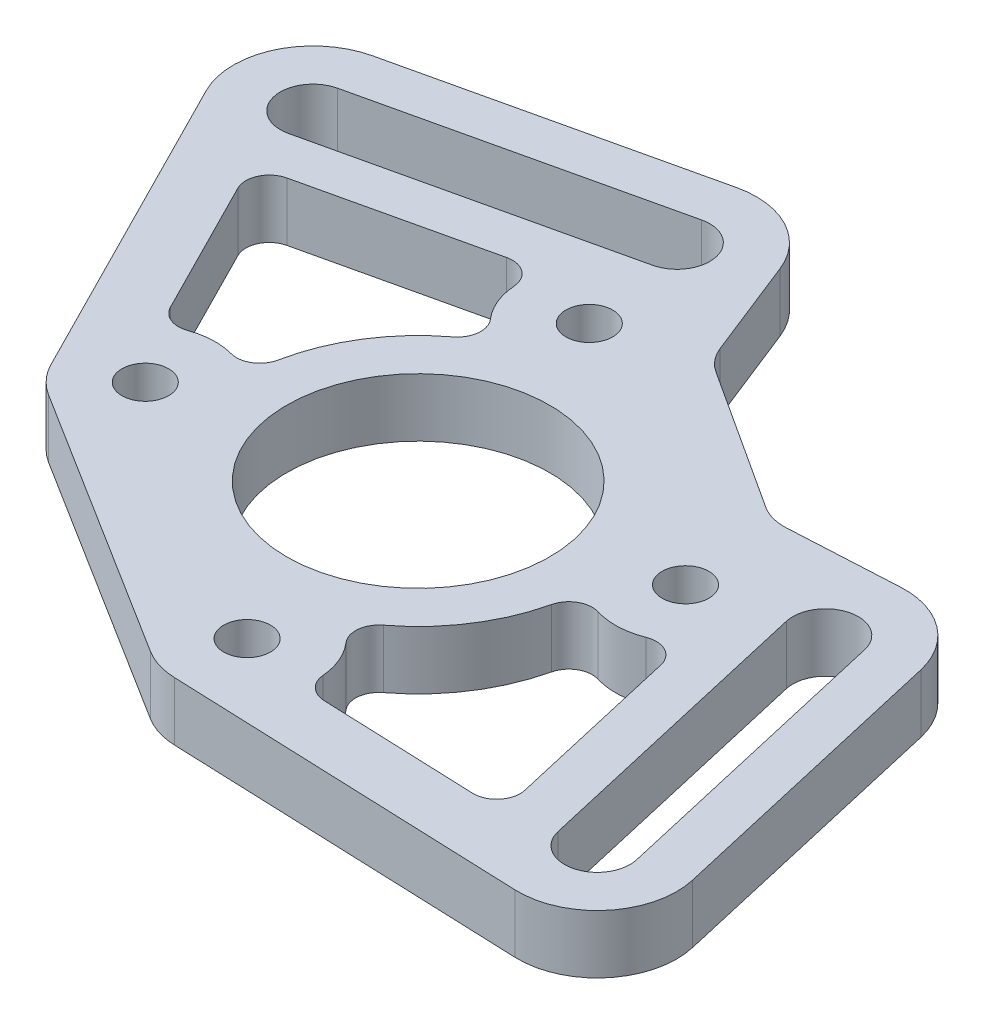
SolidWorks part; units mm, degrees
ref_plane "Front Plane" through (0, 0, 0) normal (0, 0, 1) x (1, 0, 0)
ref_plane "Top Plane" through (0, 0, 0) normal (0, 1, 0) x (1, 0, 0)
ref_plane "Right Plane" through (0, 0, 0) normal (1, 0, 0) x (0, 0, -1)
sketch "Sketch1" plane through (0, 0, 0) normal (0, 1, 0) x (1, 0, 0)
  line L0 (9.2897, 14.4451) -> (11.6941, 18.1838) construction
  line L2 (-10.3015, 44.9223) -> (-42.4861, 37.5417)
  line L3 (45.0868, 9.5277) -> (52.4673, -22.6569)
  line L4 (-5.5326, 24.1261) -> (24.2906, 4.7587) construction
  line L5 (-5.5326, 24.1261) -> (5.5326, -24.1261) construction
  line L6 (36.6692, 7.5974) -> (44.0498, -24.5872) construction
  line L7 (40.1353, 8.3922) -> (47.5158, -23.7924)
  line L8 (33.2032, 6.8025) -> (40.5838, -25.382)
  line L9 (24.2906, 4.7587) -> (36.6692, 7.5974) construction
  line L10 (-6.9454, 30.2884) -> (30.3335, 6.0792) construction
  line L11 (30.3335, 6.0792) -> (6.1243, -31.1997) construction
  line L12 (6.1243, -31.1997) -> (-31.1546, -6.9905) construction
  line L13 (-31.1546, -6.9905) -> (-6.9454, 30.2884) construction
  line L14 (-5.5326, 24.1261) -> (-8.3712, 36.5048) construction
  line L15 (-8.3712, 36.5048) -> (-40.5558, 29.1242) construction
  line L16 (9.2897, 14.4451) -> (0, 0) construction
  line L17 (-7.5764, 33.0387) -> (-39.761, 25.6582)
  line L18 (-9.1661, 39.9708) -> (-41.3507, 32.5902)
  line L19 (-55, 0) -> (55, 0) construction
  line L21 (-48.2586, 25.2194) -> (-30.9226, -8.978)
  line L22 (-28.1736, -11.9887) -> (1.4851, -30.5822)
  line L23 (5.2404, -31.7405) -> (43.7187, -33.2169)
  line L24 (36.2135, 16.2213) -> (24.4027, 15.5971)
  line L25 (-0.3414, 39.6831) -> (3.9502, 28.8409)
  line L26 (21.3678, 16.4096) -> (5.9069, 26.4501)
  line L27 (-6.4409, 28.0872) -> (-38.6255, 20.7067) construction
  line L28 (28.2517, 5.6671) -> (35.6323, -26.5175) construction
  arc A6 (-7.5764, 33.0387) -> (-9.1661, 39.9708) centre (-8.3712, 36.5048) ccw
  arc A7 (-41.3507, 32.5902) -> (-39.761, 25.6582) centre (-40.5558, 29.1242) ccw
  circle A8 centre (-5.5326, 24.1261) radius 2.54
  circle A9 centre (24.2906, 4.7587) radius 2.54
  circle A10 centre (5.5326, -24.1261) radius 2.54
  circle A11 centre (-24.1261, -5.5326) radius 2.54
  circle A12 centre (0, 0) radius 14.2875
  circle A13 centre (0, 0) radius 21.0058 construction
  arc A14 (40.1353, 8.3922) -> (33.2032, 6.8025) centre (36.6692, 7.5974) ccw
  arc A15 (40.5838, -25.382) -> (47.5158, -23.7924) centre (44.0498, -24.5872) ccw
  circle A16 centre (44.0498, -24.5872) radius 11.1125 construction
  circle A17 centre (0, 0) radius 24.7523 construction
  arc A18 (-42.4861, 37.5417) -> (-48.2586, 25.2194) centre (-40.5558, 29.1242) ccw
  arc A19 (-0.3414, 39.6831) -> (-10.3015, 44.9223) centre (-8.3712, 36.5048) ccw
  arc A20 (43.7187, -33.2169) -> (52.4673, -22.6569) centre (44.0498, -24.5872) ccw
  arc A21 (45.0868, 9.5277) -> (36.2135, 16.2213) centre (36.6692, 7.5974) ccw
  arc A22 (1.4851, -30.5822) -> (5.2404, -31.7405) centre (5.5326, -24.1261) ccw
  arc A23 (-30.9226, -8.978) -> (-28.1736, -11.9887) centre (-24.1261, -5.5326) ccw
  arc A26 (-42.4861, 37.5417) -> (-38.6255, 20.7067) centre (-40.5558, 29.1242) ccw construction
  circle A27 centre (-24.1261, -5.5326) radius 7.62 construction
  circle A28 centre (5.5326, -24.1261) radius 7.62 construction
  arc A29 (35.6323, -26.5175) -> (52.4673, -22.6569) centre (44.0498, -24.5872) ccw construction
  arc A30 (-6.4409, 28.0872) -> (-10.3015, 44.9223) centre (-8.3712, 36.5048) ccw construction
  arc A31 (45.0868, 9.5277) -> (28.2517, 5.6671) centre (36.6692, 7.5974) ccw construction
  arc A32 (21.3678, 16.4096) -> (24.4027, 15.5971) centre (24.1346, 20.6701) ccw
  arc A33 (5.9069, 26.4501) -> (3.9502, 28.8409) centre (8.6736, 30.7105) cw
  point P20 (11.6941, 18.1838)
  point P39 (40.3595, -8.4949)
  point P49 (-24.4635, 32.8145)
  dimension "D4" = 5.08
  dimension "D5" = 28.575
  dimension "D6" = 42.0116
  dimension "D13" = 49.5046
  dimension "D26" = 5.08
  dimension "D3" = 35.56
  dimension "D7" = 7.112
  dimension "D8" = 33.02
  dimension "D9" = 12.7
  dimension "D10" = 7.112
  dimension "D11" = 33.02
  dimension "D12" = 12.7
  dimension "D14" = 44.45
  dimension "D15" = 44.45
  dimension "D16" = 4.3987
  dimension "D17" = 17.7037
  dimension "D18" = 5.08
  dimension "D19" = 17.1744
  dimension "D21" = 147
  dimension "D22" = 5.08
  dimension "D25" = 25.4
  dimension "D20" = 90
  dimension "D23" = 5.08
  dimension "D24" = 5.08
extrude "Boss-Extrude1" add sketch "Sketch1" along normal blind 6.35
sketch "Sketch3" plane through (0, 6.35, 0) normal (0, 1, 0) x (1, 0, 0)
  line L3 (28.2517, 5.6671) -> (35.6323, -26.5175)
  line L4 (29.6925, -0.6156) -> (35.6323, -26.5175)
  line L13 (-38.6255, 20.7067) -> (-6.4409, 28.0872)
  line L14 (-38.6255, 20.7067) -> (-12.7237, 26.6465)
  line L16 (-42.5948, 28.0906) -> (-25.2588, -6.1068)
  line L17 (-24.8006, -6.6086) -> (4.858, -25.2021)
  line L18 (5.4839, -25.3951) -> (43.9621, -26.8715)
  line L19 (46.278, -24.0763) -> (38.8974, 8.1083)
  line L20 (36.5486, 9.8802) -> (24.7378, 9.256)
  line L21 (17.9094, 11.084) -> (2.4484, 21.1245)
  line L22 (-1.9541, 26.5038) -> (-6.2457, 37.3461)
  line L23 (-8.8822, 38.7329) -> (-41.0668, 31.3524)
  line L24 (-38.8293, 20.6626) -> (-28.6561, 0.5947)
  line L26 (12.9918, -25.6832) -> (35.6403, -26.5522)
  circle A2 centre (0, 0) radius 19.3675
  arc A3 (-8.8108, 17.2473) -> (-19.363, 0.4154) centre (0, 0) ccw
  arc A4 (8.8108, -17.2473) -> (19.3399, -1.034) centre (0, 0) ccw
  arc A5 (35.6323, -26.5175) -> (52.4673, -22.6569) centre (44.0498, -24.5872) ccw
  arc A6 (45.0868, 9.5277) -> (28.2517, 5.6671) centre (36.6692, 7.5974) ccw
  arc A7 (35.6323, -26.5175) -> (35.6403, -26.5522) centre (44.0498, -24.5872) ccw
  arc A15 (-6.4409, 28.0872) -> (-10.3015, 44.9223) centre (-8.3712, 36.5048) ccw
  arc A16 (-41.0668, 31.3524) -> (-42.5948, 28.0906) centre (-40.5558, 29.1242) ccw
  arc A17 (-25.2588, -6.1068) -> (-24.8006, -6.6086) centre (-24.1261, -5.5326) ccw
  arc A18 (4.858, -25.2021) -> (5.4839, -25.3951) centre (5.5326, -24.1261) ccw
  arc A19 (43.9621, -26.8715) -> (46.278, -24.0763) centre (44.0498, -24.5872) ccw
  arc A20 (38.8974, 8.1083) -> (36.5486, 9.8802) centre (36.6692, 7.5974) ccw
  arc A21 (17.9094, 11.084) -> (24.7378, 9.256) centre (24.1346, 20.6701) ccw
  arc A22 (-1.9541, 26.5038) -> (2.4484, 21.1245) centre (8.6736, 30.7105) ccw
  arc A23 (-6.2457, 37.3461) -> (-8.8822, 38.7329) centre (-8.3712, 36.5048) ccw
  arc A32 (-42.4861, 37.5417) -> (-38.6255, 20.7067) centre (-40.5558, 29.1242) ccw
  arc A34 (-38.8293, 20.6626) -> (-38.6255, 20.7067) centre (-40.5558, 29.1242) ccw
  circle A38 centre (-5.5326, 24.1261) radius 7.62
  arc A39 (-12.7237, 26.6465) -> (-8.8108, 17.2473) centre (-5.5326, 24.1261) ccw
  circle A41 centre (-24.1261, -5.5326) radius 7.62
  arc A42 (-19.363, 0.4154) -> (-28.6561, 0.5947) centre (-24.1261, -5.5326) ccw
  circle A44 centre (24.2906, 4.7587) radius 7.62
  arc A45 (19.3399, -1.034) -> (29.6925, -0.6156) centre (24.2906, 4.7587) ccw
  circle A47 centre (5.5326, -24.1261) radius 7.62
  arc A48 (12.9918, -25.6832) -> (8.8108, -17.2473) centre (5.5326, -24.1261) ccw
  dimension "D1" = 6.35
  dimension "D2" = 5.08
  dimension "D3" = 5.08
  dimension "D4" = 5.08
  dimension "D5" = 5.08
  dimension "D6" = 5.08
  dimension "D7" = 5.08
  dimension "D8" = 5.08
extrude "Cut-Extrude1" cut sketch "Sketch3" against normal through all
fillet "Fillet1" radius 2.54 10 edges at (35.6403, 3.175, 26.5522) (8.8108, 3.175, 17.2473) (12.9918, 3.175, 25.6832) (29.6925, 3.175, 0.6156) (19.3399, 3.175, 1.034) (-38.8293, 3.175, -20.6626) (-28.6561, 3.175, -0.5947) (-19.363, 3.175, -0.4154) (-8.8108, 3.175, -17.2473) (-12.7237, 3.175, -26.6465)
